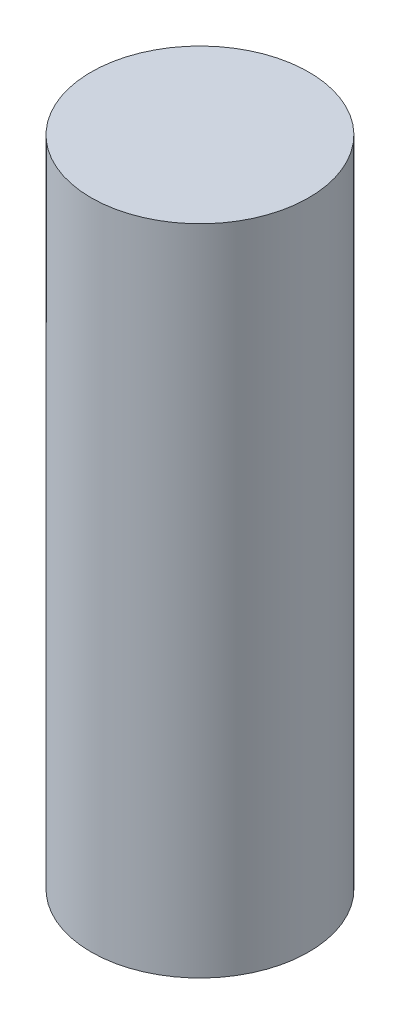
SolidWorks part; units mm, degrees
ref_plane "Front Plane" through (0, 0, 0) normal (0, 0, 1) x (1, 0, 0)
ref_plane "Top Plane" through (0, 0, 0) normal (0, 1, 0) x (1, 0, 0)
ref_plane "Right Plane" through (0, 0, 0) normal (1, 0, 0) x (0, 0, -1)
sketch "Sketch1" plane through (0, 0, 0) normal (0, 1, 0) x (1, 0, 0)
  circle A0 centre (0, 0) radius 5
  dimension "D1" = 10
extrude "Boss-Extrude1" add sketch "Sketch1" along normal blind 30
sketch "Sketch2" plane through (0, 0, 0) normal (0, -1, 0) x (1, 0, 0)
  circle A0 centre (0, 0) radius 1.8
  dimension "D1" = 3.6
extrude "Cut-Extrude1" cut sketch "Sketch2" against normal blind 3
